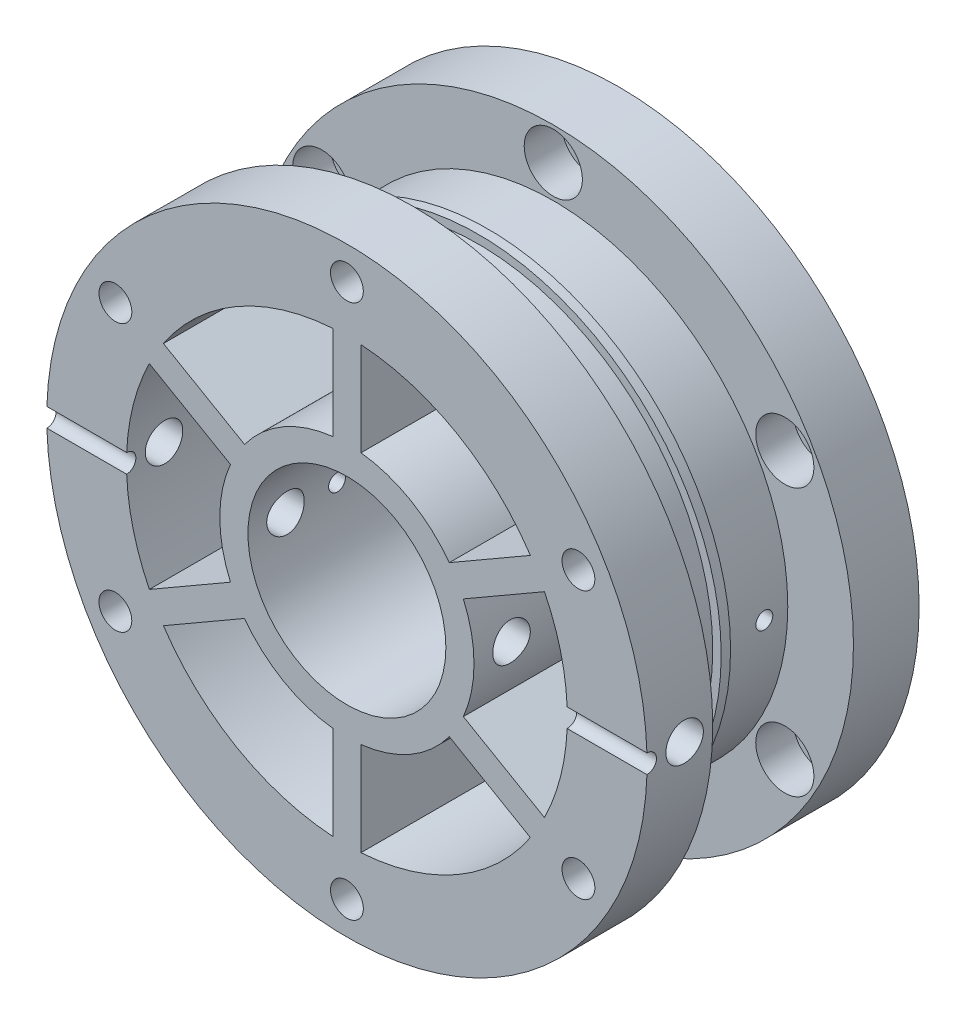
SolidWorks part; units mm, degrees
ref_plane "Front Plane" through (0, 0, 0) normal (0, 0, 1) x (1, 0, 0)
ref_plane "Top Plane" through (0, 0, 0) normal (0, 1, 0) x (1, 0, 0)
ref_plane "Right Plane" through (0, 0, 0) normal (1, 0, 0) x (0, 0, -1)
sketch "Sketch2" plane through (0, 0, 0) normal (1, 0, 0) x (0, 0, -1)
  line L8 (0, 0) -> (0, 25)
  line L9 (0, 25) -> (-7.5, 25)
  line L10 (-7.5, 25) -> (-7.5, 32)
  line L11 (-7.5, 32) -> (-14.5, 32)
  line L12 (-14.5, 32) -> (-14.5, 0)
  line L13 (-14.5, 0) -> (0, 0)
  dimension "D1" = 32
  dimension "D2" = 25
  dimension "D3" = 14.5
  dimension "D4" = 7
revolve "Revolve1" add sketch "Sketch2" angle 360 about L13
sketch "Sketch4" plane through (0, 0, 14.5) normal (0, 0, 1) x (1, 0, 0)
  line L0 (0, 18.7779) -> (0, 23.5) construction
  line L1 (-1.5, 23.4521) -> (-1.5, 13.4667)
  line L2 (0, 18.7779) -> (-1.5, 18.4594) construction
  line L3 (1.5, 23.4521) -> (1.5, 13.4667)
  line L4 (19.5601, 13.0251) -> (10.9125, 8.0324)
  line L5 (21.0601, 10.427) -> (12.4125, 5.4343)
  line L6 (21.0601, -10.427) -> (12.4125, -5.4343)
  line L7 (19.5601, -13.0251) -> (10.9125, -8.0324)
  line L8 (1.5, -23.4521) -> (1.5, -13.4667)
  line L9 (-1.5, -23.4521) -> (-1.5, -13.4667)
  line L10 (-19.5601, -13.0251) -> (-10.9125, -8.0324)
  line L11 (-21.0601, -10.427) -> (-12.4125, -5.4343)
  line L12 (-21.0601, 10.427) -> (-12.4125, 5.4343)
  line L13 (-19.5601, 13.0251) -> (-10.9125, 8.0324)
  circle A0 centre (0, 0) radius 23.5
  circle A1 centre (0, 0) radius 10.55
  arc A3 (-1.5, 13.4667) -> (-10.9125, 8.0324) centre (0, 0) ccw
  arc A4 (-12.4125, 5.4343) -> (-12.4125, -5.4343) centre (0, 0) ccw
  arc A5 (-10.9125, -8.0324) -> (-1.5, -13.4667) centre (0, 0) ccw
  arc A6 (1.5, -13.4667) -> (10.9125, -8.0324) centre (0, 0) ccw
  arc A7 (12.4125, -5.4343) -> (12.4125, 5.4343) centre (0, 0) ccw
  arc A8 (10.9125, 8.0324) -> (1.5, 13.4667) centre (0, 0) ccw
  point P34 (0, 0)
  point P37 (0, 0)
  dimension "D1" = 47
  dimension "D2" = 21.1
  dimension "D5" = 6
  dimension "D3" = 3
  dimension "D4" = 1.5
extrude "Cut-Extrude1" cut sketch "Sketch4" against normal blind 45 contours A3 L1 A0 L13 | A8 L4 A0 L3 | A7 L6 A0 L5 | A6 L8 A0 L7 | A5 L10 A0 L9 | A4 L12 A0 L11 | A1 region at (-9.2149, 15.9606, 14.5) region at (9.2149, 15.9606, 14.5) region at (-18.4297, 0, 14.5) region at (18.4297, 0, 14.5) region at (-9.2149, -15.9606, 14.5) region at (9.2149, -15.9606, 14.5)
sketch "Sketch5" plane through (0, 0, 14.5) normal (0, 0, 1) x (1, 0, 0)
  line L0 (0, 28.5) -> (0, 0) construction
  line L1 (0, 28.5) -> (0, 32) construction
  circle A0 centre (0, 28.5) radius 1.75
  circle A1 centre (0, 0) radius 32 construction
  dimension "D1" = 3.5
  dimension "D2" = 3.5
extrude "Cut-Extrude2" cut sketch "Sketch5" against normal blind 20 contours A0
sketch "Sketch14" plane through (0, 0, 7.5) normal (0, 0, -1) x (-1, 0, 0)
  circle A0 centre (0, 28.5) radius 3.1
  dimension "D1" = 6.2
extrude "Cut-Extrude9" cut sketch "Sketch14" against normal blind 4
ref_axis "Axis1" through (0, 0, 50.486) along (0, 0, -1)
pattern_circular "CirPattern1" count 6 every 60 about axis through (0, 0, 50.486) along (0, 0, -1) of "Cut-Extrude2", "Cut-Extrude9"
mirror "Mirror1" about plane through (0, 0, 0) normal (0, 0, 1) of "CirPattern1", "Cut-Extrude2", "Cut-Extrude1", "Revolve1"
sketch "Sketch6" plane through (0, 0, 0) normal (1, 0, 0) x (0, 0, -1)
  line L0 (0, 0) -> (-5, 0) construction
  line L1 (-50.486, 0) -> (29.4042, 0) construction
  line L2 (0, 0) -> (-5, 0) construction
  line L3 (0, 0) -> (5, 0) construction
  circle A0 centre (-5, 0) radius 0.9
  circle A1 centre (-5, 0) radius 0.9
  circle A2 centre (5, 0) radius 0.9
  dimension "D1" = 1.8
  dimension "D3" = 1.8
  dimension "D2" = 5
extrude "Cut-Extrude3" cut sketch "Sketch6" against normal blind 50 contours A0
extrude "Cut-Extrude4" cut sketch "Sketch6<3>" along normal blind 50 contours A2
sketch "Sketch6<3>" plane through (0, 0, 0) normal (1, 0, 0) x (0, 0, -1) same geometry as "Sketch6"
sketch "Sketch7" plane through (0, 0, 0) normal (1, 0, 0) x (0, 0, -1)
  line L0 (-7.5, 0) -> (-8.5, 0) construction
  line L3 (-7.5, -32) -> (-7.5, 32) construction
  circle A0 centre (-10.5, 0) radius 2
  dimension "D1" = 4
  dimension "D2" = 1
extrude "Cut-Extrude5" cut sketch "Sketch7" against normal through all both and the other way through all
sketch "Sketch8" plane through (0, 0, 14.5) normal (0, 0, 1) x (1, 0, 0)
  line L0 (32, 0) -> (-32, 0) construction
  circle A3 centre (0, 0) radius 32 construction
ref_plane "Plane3" through (-32, 0, 0) normal (-1, 0, 0) x (0, 0, 1)
ref_plane "Plane4" through (32, 0, 0) normal (1, 0, 0) x (0, 0, -1)
sketch "Sketch11" plane through (-32, 0, 0) normal (-1, 0, 0) x (0, 0, 1)
  line L0 (14.5, -32) -> (14.5, 32) construction
  circle A0 centre (14.5, 0) radius 1
  dimension "D1" = 2
extrude "Cut-Extrude8" cut sketch "Sketch11" against normal blind 13
mirror "Mirror2" about plane through (0, 0, 0) normal (1, 0, 0) of "Cut-Extrude8"
sketch "Sketch13" plane through (0, 0, 0) normal (0, 1, 0) x (1, 0, 0)
  line L0 (0, 0) -> (30.21, 0) construction
  line L3 (25, 0) -> (25, -0.5)
  line L4 (25, -0.5) -> (25.9, -0.5)
  line L5 (25.9, -0.5) -> (25.9, 0.5)
  line L6 (25.9, 0.5) -> (25, 0.5)
  line L7 (25, 0.5) -> (25, 0)
  dimension "D1" = 0.5
  dimension "D2" = 0.9
revolve "Revolve3" add sketch "Sketch13" angle 360 about axis through (0, 0, 50.486) along (0, 0, -1)
